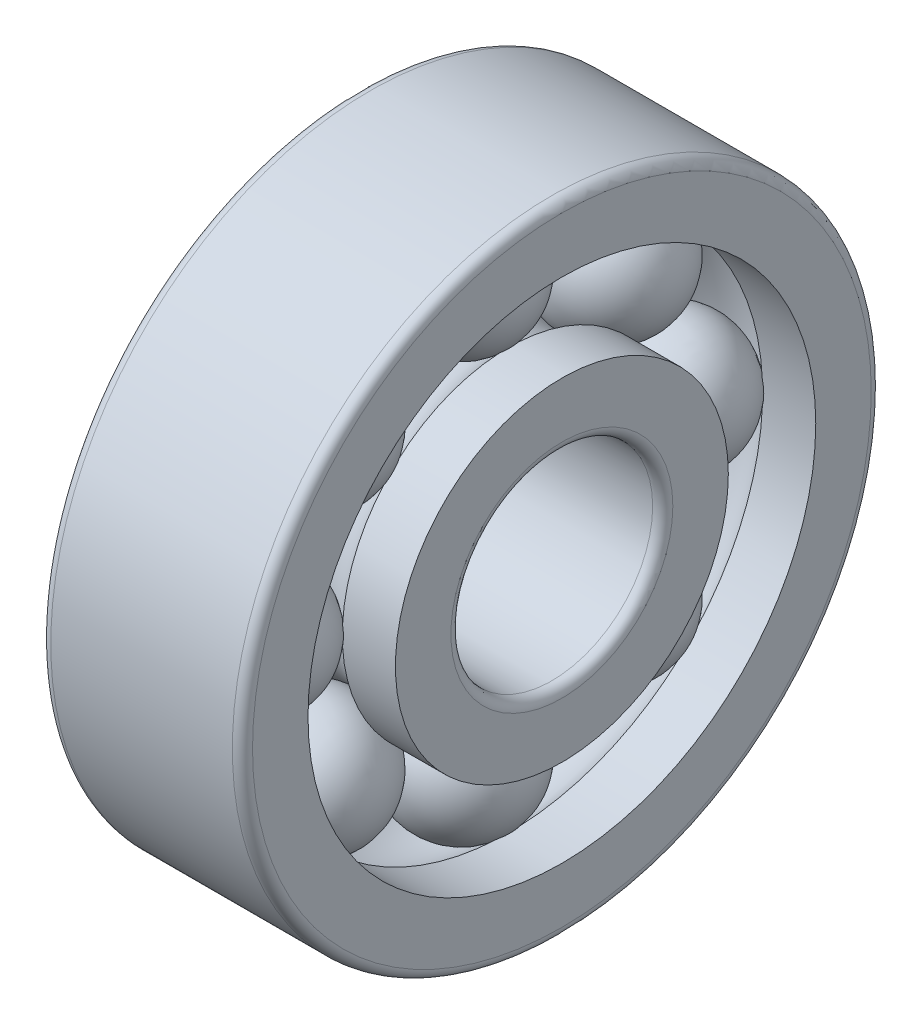
SolidWorks part; units mm, degrees
ref_plane "Plane1" through (0, 0, 0) normal (0, 0, 1) x (1, 0, 0)
ref_plane "Plane2" through (0, 0, 0) normal (0, 1, 0) x (1, 0, 0)
ref_plane "Plane3" through (0, 0, 0) normal (1, 0, 0) x (0, 0, -1)
sketch "Clipboard" plane through (0, 0, 0) normal (0, 0, 1) x (1, 0, 0)
  line L0 (-10, 0) -> (10, 0) construction
  line L1 (0, 0) -> (22.1431, -3.112)
  line L2 (0, 0) -> (6.1892, 0.8698)
  line L3 (0, 0) -> (22.1431, -3.112)
  line L4 (0, 0) -> (-22.3573, -0.3902)
  dimension "BallCLRad" = 6.25
sketch "CagSpiSke" plane through (0, 0, 0) normal (0, 0, 1) x (1, 0, 0)
  line L0 (0.195, 5.925) -> (0.195, 6.575)
  line L1 (0.195, 6.575) -> (-0.195, 6.575)
  line L2 (-0.195, 6.575) -> (-0.195, 5.925)
  line L3 (-0.195, 5.925) -> (0.195, 5.925)
  line L4 (-20.6375, 0) -> (20.6375, 0) construction
  line L5 (0, 0) -> (0, 23.7692) construction
  dimension "OD" = 13.15
  dimension "ID" = 11.85
revolve "CageSpine" add sketch "CagSpiSke" angle 0.001 about L4 reverse direction yes
ref_axis "Axis1" through (-50, 0, 0) along (1, 0, 0)
sketch "CagBalSke" plane through (0, 0, 0) normal (0, 0, 1) x (1, 0, 0)
  line L0 (-2.145, 6.25) -> (2.145, 6.25)
  line L1 (-1.905, 6.25) -> (1.905, 6.25) construction
  line L2 (-10, 0) -> (10, 0) construction
  line L3 (0, 0) -> (0, 24) construction
  arc A0 (2.145, 6.25) -> (-2.145, 6.25) centre (0, 6.25) cw
  dimension "BallCLRad" = 6.25
revolve "CageBall" [suppressed] add sketch "CagBalSke" angle 360 about L1 reverse direction yes
pattern_circular "CageBalls" [suppressed] count 8 every 45 about axis through (-50, 0, 0) along (1, 0, 0)
sketch "CagTrmODSke" plane through (0, 0, 0) normal (0, 0, 1) x (1, 0, 0)
  line L0 (2.146, 6.575) -> (2.146, 8.396)
  line L1 (2.146, 8.396) -> (-2.146, 8.396)
  line L2 (-2.146, 8.396) -> (-2.146, 6.575)
  line L3 (-2.146, 6.575) -> (2.146, 6.575)
  line L4 (-20.6375, 0) -> (20.6375, 0) construction
  line L5 (0, 0) -> (0, 25) construction
  dimension "Width" = 4.292
  dimension "ID" = 13.15
  dimension "OD" = 16.792
revolve "CageTrimOD" [suppressed] cut sketch "CagTrmODSke" angle 360 about L4 reverse direction yes
sketch "CagTrmIDSke" plane through (0, 0, 0) normal (0, 0, 1) x (1, 0, 0)
  line L0 (2.146, 4.106) -> (2.146, 5.925)
  line L1 (2.146, 5.925) -> (-2.146, 5.925)
  line L2 (-2.146, 5.925) -> (-2.146, 4.106)
  line L3 (-2.146, 4.106) -> (2.146, 4.106)
  line L4 (-20.6375, 0) -> (20.6375, 0) construction
  line L5 (0, 0) -> (0, 25) construction
  dimension "Width" = 4.292
  dimension "ID" = 8.212
  dimension "OD" = 11.85
revolve "CageTrimID" [suppressed] cut sketch "CagTrmIDSke" angle 360 about L4 reverse direction yes
sketch "BalSimSke" plane through (0, 0, 0) normal (0, 0, 1) x (1, 0, 0)
  line L0 (-10, 0) -> (10, 0) construction
  line L1 (-10, 6.25) -> (10, 6.25) construction
  line L2 (0, 0) -> (0, 23) construction
  circle A0 centre (0, 6.25) radius 1.95
  dimension "BallCLRad" = 6.25
  dimension "Ball_diameter" = 3.9
revolve "BallsSimplified" [suppressed] add sketch "BalSimSke" angle 360 about L0
sketch "BalDetSke" plane through (0, 0, 0) normal (0, 0, 1) x (1, 0, 0)
  line L0 (-1.95, 6.25) -> (1.95, 6.25)
  line L1 (-1.905, 6.25) -> (1.905, 6.25) construction
  line L2 (0, 0) -> (0, 25) construction
  arc A0 (1.95, 6.25) -> (-1.95, 6.25) centre (0, 6.25) cw
  dimension "BallCLRad" = 6.25
  dimension "Ball_diameter" = 3.9
revolve "BallDetailed" add sketch "BalDetSke" angle 360 about L1 reverse direction yes
sketch "InnRacSke" plane through (0, 0, 0) normal (0, 0, 1) x (1, 0, 0)
  line L0 (-1.4197, 4.95) -> (-3, 4.95)
  line L1 (-3, 4.95) -> (-3, 3.3)
  line L2 (-2.7, 3) -> (2.7, 3)
  line L3 (3, 3.3) -> (3, 4.95)
  line L4 (3, 4.95) -> (1.4197, 4.95)
  line L5 (-20.6375, 0) -> (20.6375, 0) construction
  line L6 (0, 0) -> (0, 30) construction
  arc A0 (-3, 3.3) -> (-2.7, 3) centre (-2.7, 3.3) ccw
  arc A1 (2.7, 3) -> (3, 3.3) centre (2.7, 3.3) ccw
  arc A2 (1.4197, 4.95) -> (-1.4197, 4.95) centre (0, 6.25) cw
  dimension "BallCLRad" = 6.25
  dimension "Fillet_radius" = 0.3
  dimension "Ball_diameter" = 3.85
  dimension "ID" = 6
  dimension "OD" = 9.9
  dimension "Width" = 6
revolve "InnerRace" add sketch "InnRacSke" angle 360 about L5 reverse direction yes
sketch "OutRacSke" plane through (0, 0, 0) normal (0, 0, 1) x (1, 0, 0)
  line L0 (-1.4197, 7.55) -> (-3, 7.55)
  line L1 (-3, 7.55) -> (-3, 9.2)
  line L2 (-2.7, 9.5) -> (2.7, 9.5)
  line L3 (3, 9.2) -> (3, 7.55)
  line L4 (3, 7.55) -> (1.4197, 7.55)
  line L5 (-20.6375, 0) -> (20.6375, 0) construction
  line L6 (0, 0) -> (0, 30) construction
  arc A0 (-3, 9.2) -> (-2.7, 9.5) centre (-2.7, 9.2) cw
  arc A1 (2.7, 9.5) -> (3, 9.2) centre (2.7, 9.2) cw
  arc A2 (1.4197, 7.55) -> (-1.4197, 7.55) centre (0, 6.25) ccw
  dimension "BallCLRad" = 6.25
  dimension "Fillet_radius" = 0.3
  dimension "Ball_diameter" = 3.85
  dimension "Width" = 6
revolve "OuterRace" add sketch "OutRacSke" angle 360 about L5 reverse direction yes
pattern_circular "BallsDetailed" count 8 every 45 about axis through (-50, 0, 0) along (1, 0, 0) of "BallDetailed"
equation "\"BallCLRad@Clipboard\" = ( \"OD@OutRacSke\" + \"ID@InnRacSke\" ) / 4"
equation "\"BallCLRad@BalSimSke\" = \"BallCLRad@Clipboard\""
equation "\"BallCLRad@BalDetSke\" = \"BallCLRad@Clipboard\""
equation "\"BallCLRad@InnRacSke\" = \"BallCLRad@Clipboard\""
equation "\"BallCLRad@OutRacSke\" = \"BallCLRad@Clipboard\""
equation "\"Ball_diameter@InnRacSke\" = \"Ball_diameter@BalDetSke\" - 0.05"
equation "\"Ball_diameter@OutRacSke\" = \"Ball_diameter@BalDetSke\" - 0.05"
equation "\"Ball_diameter@BalSimSke\" = \"Ball_diameter@BalDetSke\""
equation "\"Width@OutRacSke\" = \"Width@InnRacSke\""
equation "\"Fillet_radius@OutRacSke\" = \"Fillet_radius@InnRacSke\""
equation "\"Max_count@Clipboard\" = int( 3.14159265 / atn(( \"Ball_diameter@BalDetSke\" / 2) / sqr( \"BallCLRad@Clipboard\"  *  \"BallCLRad@Clipboard\" - ( \"Ball_diameter@BalDetSke\" / 2) *  ( \"Ball_diameter@BalDetSke\" / 2))))"
equation "\"Max_count@Clipboard\" = ((sgn( \"Max_count@Clipboard\" - \"Count@Clipboard\" )-1)*( \"Max_count@Clipboard\" - \"Count@Clipboard\" ))/-2+ \"Count@Clipboard\""
equation "\"Count@BallsDetailed\" = int( \"Show_count@Clipboard\" ) "
equation "\"Count@BallsDetailed\" = ((sgn( \"Count@BallsDetailed\" - \"Max_count@Clipboard\" )-1)*( \"Count@BallsDetailed\" - \"Max_count@Clipboard\" ))/-2+ \"Max_count@Clipboard\""
equation "\"Count@BallsDetailed\" = ((sgn( \"Count@BallsDetailed\" - \"Min_count@Clipboard\" )+1)*( \"Count@BallsDetailed\" - \"Min_count@Clipboard\"))/2 +\"Min_count@Clipboard\""
equation "\"Angle@BallsDetailed\" = 360.0 / \"Max_count@Clipboard\""
equation "\"BallCLRad@CagBalSke\" = \"BallCLRad@Clipboard\""
equation "\"Count@CageBalls\" = \"Count@BallsDetailed\""
equation "\"Angle@CageBalls\" = \"Angle@BallsDetailed\""
equation "\"Angle@CageSpine\" =  \"Angle@CageBalls\" * ( \"Count@CageBalls\" -1 + int( \"Count@CageBalls\" / \"Max_count@Clipboard\" ) )  + 0.001 -  int( \"Count@CageBalls\" / \"Max_count@Clipboard\" ) * 0.001"
equation "\"Angle@CageSpine\" =  \"Angle@CageSpine\" * int( \"Min_count@Clipboard\" / 2) + int(1 / \"Min_count@Clipboard\")  * 0.001"
equation "\"CageWallOD@CagBalSke\" =  \"Ball_diameter@BalDetSke\" * 1.1"
equation "\"Thickness@CagSpiSke\" =  \"Ball_diameter@BalDetSke\" * 0.1"
equation "\"OD@CagTrmODSke\" = \"BallCLRad@Clipboard\" * 2 + \"CageWallOD@CagBalSke\" + 0.002"
equation "\"ID@CagTrmODSke\" = \"BallCLRad@Clipboard\" * 2 + \"Ball_diameter@BalDetSke\" / 6"
equation "\"OD@CagTrmIDSke\" = \"BallCLRad@Clipboard\" * 2 - \"Ball_diameter@BalDetSke\" / 6"
equation "\"ID@CagTrmIDSke\" = \"BallCLRad@Clipboard\" * 2 - \"CageWallOD@CagBalSke\" + 0.002"
equation "\"OD@CagSpiSke\" = \"ID@CagTrmODSke\""
equation "\"ID@CagSpiSke\" = \"OD@CagTrmIDSke\""
equation "\"Width@CagTrmODSke\" = \"CageWallOD@CagBalSke\" + 0.002"
equation "\"Width@CagTrmIDSke\" = \"CageWallOD@CagBalSke\" + 0.002"
